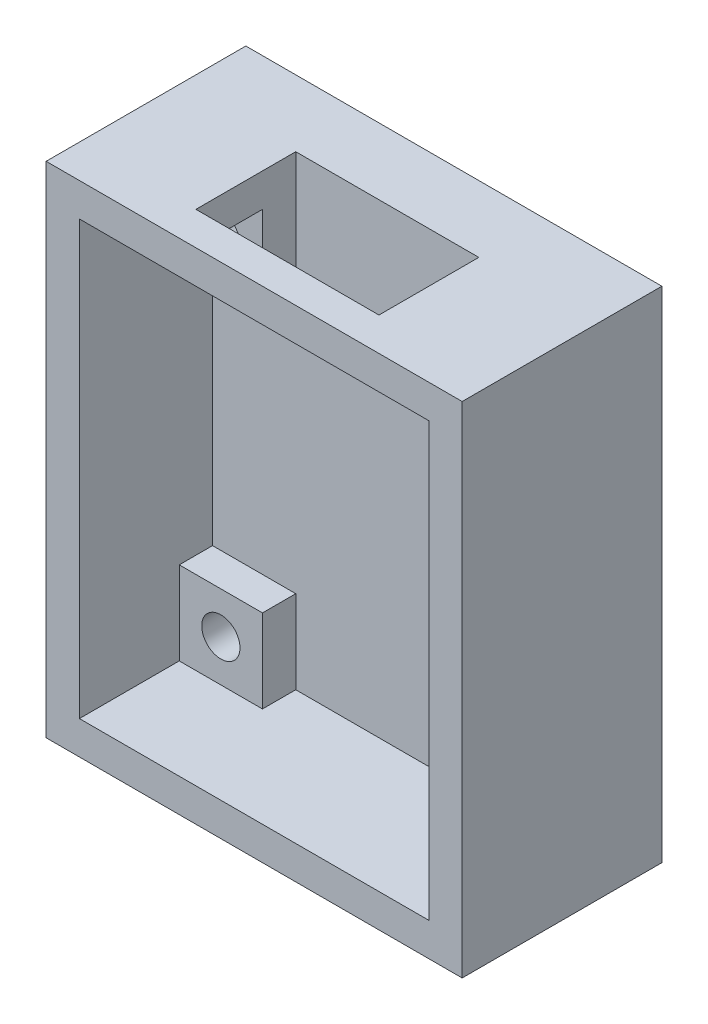
SolidWorks part; units mm, degrees
ref_plane "正面" through (0, 0, 0) normal (0, 0, 1) x (1, 0, 0)
ref_plane "平面" through (0, 0, 0) normal (0, 1, 0) x (1, 0, 0)
ref_plane "右側面" through (0, 0, 0) normal (1, 0, 0) x (0, 0, -1)
sketch "ｽｹｯﾁ1" plane through (0, 0, 0) normal (0, 0, 1) x (1, 0, 0)
  line L1 (-83.9031, 40.6786) -> (-58.9031, 40.6786)
  line L2 (-83.9031, 40.6786) -> (-83.9031, 10.6786)
  line L3 (-83.9031, 10.6786) -> (-58.9031, 10.6786)
  line L4 (-58.9031, 40.6786) -> (-58.9031, 10.6786)
  dimension "D1" = 30
  dimension "D2" = 25
extrude "ﾎﾞｽ - 押し出し1" add sketch "ｽｹｯﾁ1" along normal blind 12
sketch "ｽｹｯﾁ2" plane through (0, 0, 12) normal (0, 0, 1) x (1, 0, 0)
  line L0 (-58.9031, 40.6786) -> (-83.9031, 40.6786) construction
  line L1 (-81.9031, 38.6786) -> (-60.9031, 38.6786)
  line L2 (-81.9031, 38.6786) -> (-81.9031, 12.6786)
  line L3 (-81.9031, 12.6786) -> (-60.9031, 12.6786)
  line L4 (-60.9031, 38.6786) -> (-60.9031, 12.6786)
  line L5 (-83.9031, 10.6786) -> (-58.9031, 10.6786) construction
  line L6 (-58.9031, 10.6786) -> (-58.9031, 40.6786) construction
  line L7 (-83.9031, 40.6786) -> (-83.9031, 10.6786) construction
  dimension "D1" = 26
  dimension "D2" = 21
  dimension "D3" = 2
  dimension "D4" = 2
  dimension "D5" = 2
  dimension "D6" = 2
extrude "ｶｯﾄ - 押し出し1" cut sketch "ｽｹｯﾁ2" against normal blind 8
sketch "ｽｹｯﾁ4" plane through (0, 0, 4) normal (0, 0, 1) x (1, 0, 0)
  line L1 (-60.9031, 38.6786) -> (-65.9031, 38.6786)
  line L2 (-60.9031, 38.6786) -> (-60.9031, 33.6786)
  line L3 (-60.9031, 33.6786) -> (-65.9031, 33.6786)
  line L4 (-65.9031, 38.6786) -> (-65.9031, 33.6786)
  line L5 (-60.9031, 12.6786) -> (-65.9031, 12.6786)
  line L6 (-60.9031, 12.6786) -> (-60.9031, 17.6786)
  line L7 (-60.9031, 17.6786) -> (-65.9031, 17.6786)
  line L8 (-65.9031, 12.6786) -> (-65.9031, 17.6786)
  line L9 (-81.9031, 12.6786) -> (-76.9031, 12.6786)
  line L10 (-81.9031, 12.6786) -> (-81.9031, 17.6786)
  line L11 (-81.9031, 17.6786) -> (-76.9031, 17.6786)
  line L12 (-76.9031, 12.6786) -> (-76.9031, 17.6786)
  line L13 (-81.9031, 38.6786) -> (-76.9031, 38.6786)
  line L14 (-81.9031, 38.6786) -> (-81.9031, 33.6786)
  line L15 (-81.9031, 33.6786) -> (-76.9031, 33.6786)
  line L16 (-76.9031, 38.6786) -> (-76.9031, 33.6786)
  dimension "D1" = 5
  dimension "D2" = 5
  dimension "D3" = 5
  dimension "D4" = 5
  dimension "D5" = 5
  dimension "D6" = 5
  dimension "D7" = 5
extrude "ﾎﾞｽ - 押し出し2" add sketch "ｽｹｯﾁ4" along normal blind 2
sketch "ｽｹｯﾁ5" plane through (0, 38.6786, 0) normal (0, -1, 0) x (-1, 0, 0)
  line L0 (60.9031, -12) -> (81.9031, -12) construction
  line L1 (65.9031, -4) -> (76.9031, -4)
  line L2 (65.9031, -4) -> (65.9031, -10)
  line L3 (65.9031, -10) -> (76.9031, -10)
  line L4 (76.9031, -4) -> (76.9031, -10)
  dimension "D1" = 6
  dimension "D2" = 11
  dimension "D3" = 2
extrude "ｶｯﾄ - 押し出し3" cut sketch "ｽｹｯﾁ5" against normal through all
sketch "ｽｹｯﾁ6" plane through (0, 0, 6) normal (0, 0, 1) x (1, 0, 0)
  line L0 (-65.9031, 33.6786) -> (-60.9031, 33.6786) construction
  line L1 (-65.9031, 38.6786) -> (-65.9031, 33.6786) construction
  line L2 (-81.9031, 33.6786) -> (-76.9031, 33.6786) construction
  line L3 (-76.9031, 33.6786) -> (-76.9031, 38.6786) construction
  line L4 (-76.9031, 12.6786) -> (-76.9031, 17.6786) construction
  line L5 (-76.9031, 17.6786) -> (-81.9031, 17.6786) construction
  line L6 (-65.9031, 17.6786) -> (-65.9031, 12.6786) construction
  line L7 (-60.9031, 17.6786) -> (-65.9031, 17.6786) construction
  circle A0 centre (-63.4031, 36.1786) radius 1.15
  circle A1 centre (-63.4031, 15.1786) radius 1.15
  circle A2 centre (-79.4031, 36.1786) radius 1.15
  circle A3 centre (-79.4031, 15.1786) radius 1.15
  dimension "D1" = 2.3
  dimension "D2" = 2.5
  dimension "D4" = 2.5
  dimension "D6" = 2.5
  dimension "D7" = 2.5
  dimension "D8" = 2.5
  dimension "D9" = 2.5
  dimension "D3" = 2.5
  dimension "D5" = 2.5
extrude "ｶｯﾄ - 押し出し4" cut sketch "ｽｹｯﾁ6" against normal through all
